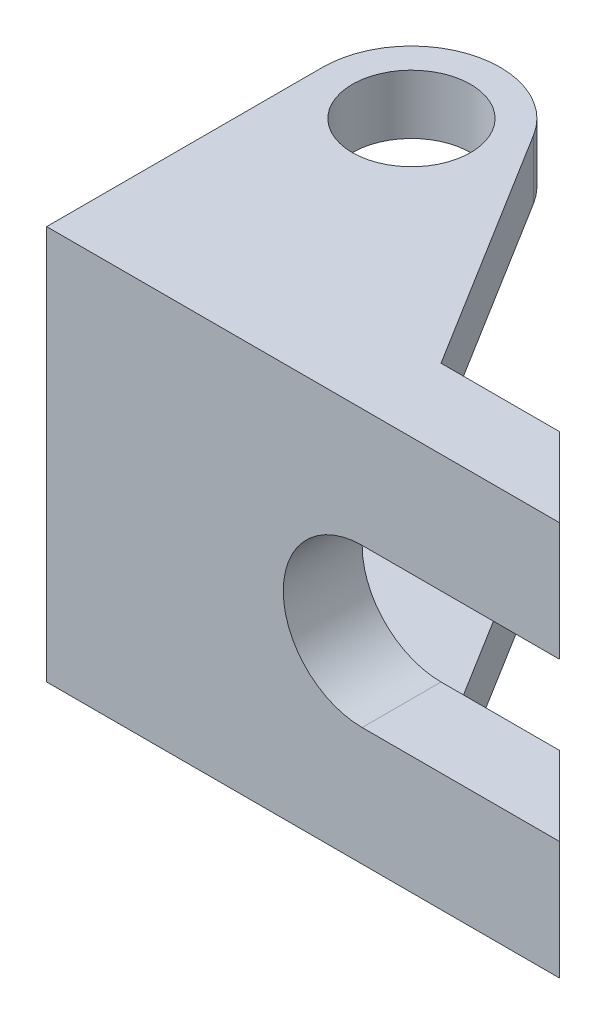
SolidWorks part; units mm, degrees
ref_plane "Front Plane" through (0, 0, 0) normal (0, 0, 1) x (1, 0, 0)
ref_plane "Top Plane" through (0, 0, 0) normal (0, 1, 0) x (1, 0, 0)
ref_plane "Right Plane" through (0, 0, 0) normal (1, 0, 0) x (0, 0, -1)
sketch "Sketch1" plane through (0, 0, 0) normal (0, 1, 0) x (1, 0, 0)
  line L0 (-23.3808, 46.862) -> (15, -15)
  line L1 (65, -35) -> (-65, -35)
  line L2 (65, -35) -> (65, 35)
  line L3 (65, 35) -> (-65, 35)
  line L4 (-65, -35) -> (-65, 35)
  line L5 (65, -35) -> (-65, 35) construction
  line L6 (65, 35) -> (-65, -35) construction
  line L7 (65, -35) -> (45, -15)
  line L8 (45, -15) -> (15, -15)
  circle A0 centre (-42.5, 35) radius 22.5
  circle A1 centre (-42.5, 35) radius 15
  point P0 (0, 0)
  dimension "D3" = 45
  dimension "D7" = 30
  dimension "D1" = 130
  dimension "D2" = 70
  dimension "D4" = 20
  dimension "D5" = 30
  dimension "D6" = 20
extrude "Boss-Extrude1" add sketch "Sketch1" along normal blind 100 contours A0 L4 L1 L7 L8 L0 L3 | A1 L3 A0 | A1 L3 A0 | A0 L3 L0 | A0 | A1 region at (-19.1285, 0, -38.06) region at (-21.3456, 0, -41.0293) region at (-16.8729, 0, 11.4145) region at (-42.5, 0, -13.0031)
sketch "Sketch2" plane through (0, 0, 15) normal (0, 0, -1) x (-1, 0, 0)
  line L0 (-115, 50) -> (-15, 50) construction
  line L1 (-65, 100) -> (-65, 0) construction
  line L2 (-115, 70) -> (-15, 70)
  line L3 (-115, 30) -> (-15, 30)
  line L5 (-106.9938, 15) -> (76.9938, 15)
  line L6 (-106.9938, 15) -> (-106.9938, 85)
  line L7 (-106.9938, 85) -> (76.9938, 85)
  line L8 (76.9938, 15) -> (76.9938, 85)
  line L9 (-106.9938, 15) -> (76.9938, 85) construction
  line L10 (-106.9938, 85) -> (76.9938, 15) construction
  arc A0 (-115, 70) -> (-115, 30) centre (-115, 50) ccw
  arc A1 (-15, 30) -> (-15, 70) centre (-15, 50) ccw
  point P4 (-65, 50)
  point P10 (-15, 50)
  line M3 (-15, 0) -> (-15, 100)
  line M5 (-45, 100) -> (-45, 0)
  dimension "D1" = 20
  dimension "D2" = 50
  dimension "D3" = 70
extrude "Cut-Extrude1" cut sketch "Sketch2" along normal through all contours L7 L2 M5 M3 | A1 L5 L8 L7 M3 | L5 L3 M5 M3 region at (30, 77.5, 15) region at (-35.0524, 50, 15) region at (30, 22.5, 15)
extrude "Cut-Extrude3" cut sketch "Sketch2<3>" against normal through all and the other way through all contours L3 L2 M5 M3 | L6 L3 L2 M5 | A1 M3 region at (75.9969, 50, 15) region at (30, 50, 15) region at (6.5117, 50, 15)
sketch "Sketch2<3>" plane through (0, 0, 15) normal (0, 0, -1) x (-1, 0, 0) same geometry as "Sketch2"
